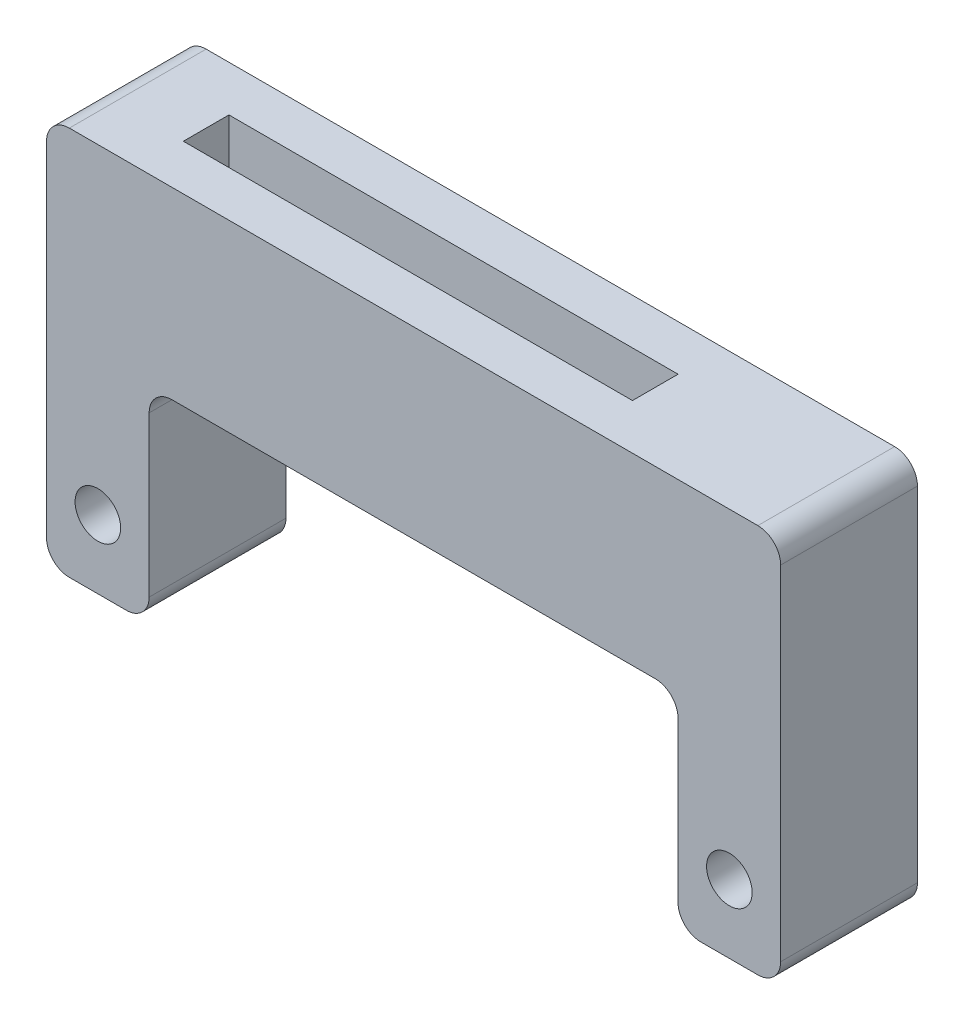
SolidWorks part; units mm, degrees
ref_plane "Front Plane" through (0, 0, 0) normal (0, 0, 1) x (1, 0, 0)
ref_plane "Top Plane" through (0, 0, 0) normal (0, 1, 0) x (1, 0, 0)
ref_plane "Right Plane" through (0, 0, 0) normal (1, 0, 0) x (0, 0, -1)
sketch "Sketch2" plane through (0, 0, 0) normal (0, 0, 1) x (1, 0, 0)
  line L1 (-16.1, -8.534) -> (16.1, -8.534)
  line L2 (-16.1, -8.534) -> (-16.1, 8.534)
  line L3 (-16.1, 8.534) -> (16.1, 8.534)
  line L4 (16.1, -8.534) -> (16.1, 8.534)
  line L5 (-16.1, -8.534) -> (16.1, 8.534) construction
  line L6 (-16.1, 8.534) -> (16.1, -8.534) construction
  point P0 (0, 0)
  dimension "D1" = 17.068
  dimension "D2" = 32.2
extrude "Boss-Extrude1" add sketch "Sketch2" along normal mid plane 6
sketch "Sketch3" plane through (0, 8.534, 0) normal (0, 1, 0) x (1, 0, 0)
  line L0 (-16.1, -3) -> (-16.1, 3) construction
  line L1 (-12.1, 1) -> (7.6, 1)
  line L2 (-12.1, 1) -> (-12.1, -1)
  line L3 (-12.1, -1) -> (7.6, -1)
  line L4 (7.6, 1) -> (7.6, -1)
  line L5 (16.1, -3) -> (16.1, 3) construction
  line L6 (16.1, 3) -> (-16.1, 3) construction
  dimension "D1" = 2
  dimension "D2" = 4
  dimension "D3" = 8.5
  dimension "D4" = 2
extrude "Cut-Extrude1" cut sketch "Sketch3" against normal blind 2.5
sketch "Sketch4" plane through (0, 0, 3) normal (0, 0, 1) x (1, 0, 0)
  line L0 (-16.1, -8.534) -> (16.1, -8.534) construction
  line L1 (-11.6, -8.534) -> (11.6, -8.534)
  line L2 (-11.6, -8.534) -> (-11.6, 0.466)
  line L3 (-11.6, 0.466) -> (11.6, 0.466)
  line L4 (11.6, -8.534) -> (11.6, 0.466)
  line L5 (-16.1, 8.534) -> (-16.1, -8.534) construction
  line L6 (16.1, -8.534) -> (16.1, 8.534) construction
  dimension "D1" = 9
  dimension "D2" = 4.5
  dimension "D3" = 4.5
extrude "Cut-Extrude2" cut sketch "Sketch4" against normal through all
sketch "Sketch5" plane through (0, 0, 3) normal (0, 0, 1) x (1, 0, 0)
  line L0 (-16.1, 8.534) -> (-16.1, -8.534) construction
  line L1 (16.1, -8.534) -> (16.1, 8.534) construction
  line L2 (-16.1, -8.534) -> (-11.6, -8.534) construction
  circle A0 centre (-13.85, -5.534) radius 1
  circle A2 centre (13.85, -5.534) radius 1
  dimension "D1" = 2
  dimension "D2" = 2.25
  dimension "D3" = 2.25
  dimension "D4" = 3
extrude "Cut-Extrude3" cut sketch "Sketch5" against normal through all
fillet "Fillet1" radius 1 8 edges at (16.1, 8.534, 0) (16.1, -8.534, 0) (11.6, -8.534, 0) (11.6, 0.466, 0) (-11.6, 0.466, 0) (-11.6, -8.534, 0) (-16.1, -8.534, 0) (-16.1, 8.534, 0)
scale "Scale1" scale about centroid uniform scaling yes scale factor 1.02
